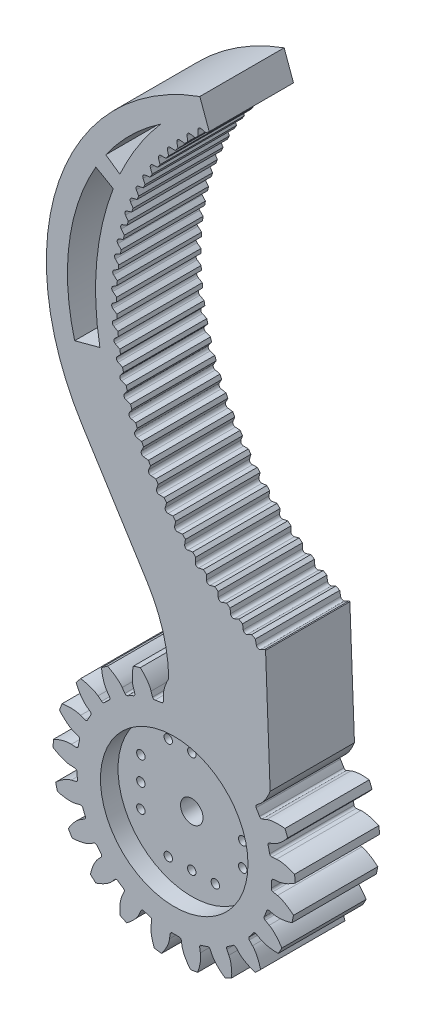
SolidWorks part; units mm, degrees
ref_plane "Спереди" through (0, 0, 0) normal (0, 0, 1) x (1, 0, 0)
ref_plane "Сверху" through (0, 0, 0) normal (0, 1, 0) x (1, 0, 0)
ref_plane "Справа" through (0, 0, 0) normal (1, 0, 0) x (0, 0, -1)
sketch "Эскиз1" plane through (0, 0, 0) normal (0, 0, 1) x (1, 0, 0)
  line L0 (15.6867, 1.4109) -> (0, 0) construction
  circle A0 centre (0, 0) radius 13.875
  circle A1 centre (0, 0) radius 14.8002
  circle A2 centre (0, 0) radius 15.75 construction
  circle A3 centre (0, 0) radius 17.25
  arc A4 (15.7483, 0.2347) -> (15.5374, 2.5792) centre (0, 0) ccw
  spline S0 degree 4 poles (14.8002, 0) (14.8458, 0.002) (14.9732, 0.0136) (15.2133, 0.0598) (15.5951, 0.1687) (16.0737, 0.3584) (16.6643, 0.6565) (17.3197, 1.0707) (17.995, 1.5895) (18.8399, 2.3661) (19.5994, 3.2279) (20.3031, 4.1917) (21.0383, 5.4087) (21.672, 6.6826) (22.2673, 8.2245) (22.7566, 9.9949) (23.0815, 11.8022) (23.2494, 13.6306) (23.2682, 15.4662) (23.1448, 17.2979) (22.8867, 19.1147) (22.5485, 20.6854) (22.2139, 21.9004) (21.9356, 22.776) (21.7516, 23.3151) (21.593, 23.7537) (21.4373, 24.1684) (21.2567, 24.6196) (21.1147, 24.9658) (20.9433, 25.3602) (20.7668, 25.7564) (20.5837, 26.1503) (20.2525, 26.8364) (19.9608, 27.3858) (19.6554, 27.9549) (19.4953, 28.2253) (19.392, 28.4076) knots 0 0 0 0 0 0.005604 0.015718 0.02996 0.048734 0.068727 0.096889 0.125051 0.153212 0.209535 0.237696 0.271429 0.327752 0.384075 0.440398 0.496721 0.553044 0.609367 0.66569 0.722013 0.778336 0.806497 0.820578 0.834659 0.84874 0.86282 0.876901 0.890982 0.900036 0.909091 0.931818 0.954545 0.977273 1 1 1 1 1 construction
  spline S1 degree 4 poles (14.8002, 0) (14.8458, 0.002) (14.9732, 0.0136) (15.2133, 0.0598) (15.5951, 0.1687) (16.0737, 0.3584) (16.6643, 0.6565) (17.3197, 1.0707) (17.995, 1.5895) (18.8399, 2.3661) (19.5994, 3.2279) (20.3031, 4.1917) (21.0383, 5.4087) (21.672, 6.6826) (22.2673, 8.2245) (22.7566, 9.9949) (23.0815, 11.8022) (23.2494, 13.6306) (23.2682, 15.4662) (23.1448, 17.2979) (22.8867, 19.1147) (22.5485, 20.6854) (22.2139, 21.9004) (21.9356, 22.776) (21.7516, 23.3151) (21.593, 23.7537) (21.4373, 24.1684) (21.2567, 24.6196) (21.1147, 24.9658) (20.9433, 25.3602) (20.8398, 25.5924) (20.7843, 25.7149) (20.7565, 25.7758) knots 0 0 0 0 0 0.005604 0.015718 0.02996 0.048734 0.068727 0.096889 0.125051 0.153212 0.209535 0.237696 0.271429 0.327752 0.384075 0.440398 0.496721 0.553044 0.609367 0.66569 0.722013 0.778336 0.806497 0.820578 0.834659 0.84874 0.86282 0.876901 0.890982 0.900036 0.909091 0.909091 0.909091 0.909091 0.909091
  dimension "D1" = 27.75
  dimension "D2" = 29.6003
  dimension "D3" = 31.5
  dimension "D4" = 34.5
  dimension "D5" = 2.3562
extrude "Бобышка-Вытянуть1" add sketch "Эскиз1" along normal mid plane 12 contours A0 region at (0, 0, 0)
sketch "Эскиз2" plane through (0, 0, 0) normal (0, 0, 1) x (1, 0, 0)
  line L0 (15.6867, 1.4109) -> (0, 0) construction
  line L1 (15.6867, 1.4109) -> (0, 0) construction
  line L2 (14.8002, 0) -> (13.8748, -0.0832)
  line L3 (14.5626, 2.6409) -> (13.6372, 2.5577)
  circle A0 centre (0, 0) radius 14.8002 construction
  circle A1 centre (0, 0) radius 14.8002
  circle A2 centre (0, 0) radius 13.875 construction
  circle A3 centre (0, 0) radius 13.875
extrude "Бобышка-Вытянуть2" add sketch "Эскиз2" along normal mid plane 12 contours L1 A1 L3 A3 | A1 L1 A3 L2 region at (14.3189, 0.6218, 0) region at (14.2001, 1.9432, 0)
sketch "Эскиз3" plane through (0, 0, 0) normal (0, 0, 1) x (1, 0, 0)
  line L0 (15.6867, 1.4109) -> (0, 0) construction
  line L1 (15.6867, 1.4109) -> (0, 0) construction
  circle A0 centre (0, 0) radius 17.25 construction
  circle A1 centre (0, 0) radius 14.8002 construction
  circle A2 centre (0, 0) radius 17.25
  circle A3 centre (0, 0) radius 14.8002
  spline S0 degree 4 poles (5.9786, 999.9569) (7.8641, 34.1268) (10.739, 0.6192) (13.3133, -0.4819) (15.5951, 0.1687) (16.0737, 0.3584) (16.6643, 0.6565) (17.3197, 1.0707) (17.995, 1.5895) (18.8399, 2.3661) (19.5994, 3.2279) (20.3031, 4.1917) (21.0383, 5.4087) (21.672, 6.6826) (22.2673, 8.2245) (22.7566, 9.9949) (23.0815, 11.8022) (23.2494, 13.6306) (23.2682, 15.4662) (23.1448, 17.2979) (22.8867, 19.1147) (22.5485, 20.6854) (22.2139, 21.9004) (21.9356, 22.776) (21.7516, 23.3151) (21.593, 23.7537) (21.4373, 24.1684) (21.2567, 24.6196) (21.1147, 24.9658) (19.98, 27.5761) (20.2039, 26.5951) (13.0579, 41.2248) (-396.3983, 934.5059) knots -0.242482 -0.242482 -0.242482 -0.242482 -0.242482 0.005604 0.015718 0.02996 0.048734 0.068727 0.096889 0.125051 0.153212 0.209535 0.237696 0.271429 0.327752 0.384075 0.440398 0.496721 0.553044 0.609367 0.66569 0.722013 0.778336 0.806497 0.820578 0.834659 0.84874 0.86282 0.876901 0.890982 0.900036 1.16908 1.16908 1.16908 1.16908 1.16908 only from (14.8002, 0) to (20.7565, 25.7758) construction
  spline S1 degree 4 poles (14.8002, 0) (14.8458, 0.002) (14.9732, 0.0136) (15.2133, 0.0598) (15.5951, 0.1687) (16.0737, 0.3584) (16.6643, 0.6565) (17.3197, 1.0707) (17.995, 1.5895) (18.8399, 2.3661) (19.5994, 3.2279) (20.3031, 4.1917) (21.0383, 5.4087) (21.672, 6.6826) (22.2673, 8.2245) (22.7566, 9.9949) (23.0815, 11.8022) (23.2494, 13.6306) (23.2682, 15.4662) (23.1448, 17.2979) (22.8867, 19.1147) (22.5485, 20.6854) (22.2139, 21.9004) (21.9356, 22.776) (21.7516, 23.3151) (21.593, 23.7537) (21.4373, 24.1684) (21.2567, 24.6196) (21.1147, 24.9658) (20.9433, 25.3602) (20.8398, 25.5924) (20.7843, 25.7149) (20.7565, 25.7758) knots 0 0 0 0 0 0.005604 0.015718 0.02996 0.048734 0.068727 0.096889 0.125051 0.153212 0.209535 0.237696 0.271429 0.327752 0.384075 0.440398 0.496721 0.553044 0.609367 0.66569 0.722013 0.778336 0.806497 0.820578 0.834659 0.84874 0.86282 0.876901 0.890982 0.900036 0.909091 0.909091 0.909091 0.909091 0.909091
  spline S2 degree 4 poles (14.5626, 2.6409) (14.6079, 2.6471) (14.7353, 2.6584) (14.9798, 2.6558) (15.3749, 2.6168) (15.8797, 2.5156) (16.514, 2.3276) (17.2328, 2.037) (17.9899, 1.647) (18.9597, 1.0336) (19.8608, 0.3212) (20.7252, -0.5016) (21.6658, -1.5679) (22.5166, -2.7082) (23.3776, -4.1192) (24.1749, -5.7738) (24.817, -7.4941) (25.3085, -9.2632) (25.6545, -11.066) (25.86, -12.8903) (25.9302, -14.7241) (25.8777, -16.3299) (25.7653, -17.585) (25.6477, -18.4963) (25.5629, -19.0596) (25.4851, -19.5194) (25.4058, -19.9552) (25.3087, -20.4315) (25.2307, -20.7975) (25.1324, -21.2161) (25.0721, -21.463) (25.0393, -21.5935) (25.0228, -21.6584) knots 0 0 0 0 0 0.005604 0.015718 0.02996 0.048734 0.068727 0.096889 0.125051 0.153212 0.209535 0.237696 0.271429 0.327752 0.384075 0.440398 0.496721 0.553044 0.609367 0.66569 0.722013 0.778336 0.806497 0.820578 0.834659 0.84874 0.86282 0.876901 0.890982 0.900036 0.909091 0.909091 0.909091 0.909091 0.909091 only from (13.85, 2.6188) to (23.9848, -20.4482)
extrude "Бобышка-Вытянуть3" add sketch "Эскиз3" along normal mid plane 12 contours A3 S1 A2 region at (15.7857, 1.4198, 0)
fillet "Скругление1" radius 0.3 2 edges at (13.6372, 2.5577, 0) (13.8748, -0.0832, 0)
pattern_circular "Круговой массив1" count 21 over 360 about axis through (0, 0, 6) along (0, 0, 1) of "Бобышка-Вытянуть3", "Скругление1", "Бобышка-Вытянуть2"
sketch "Эскиз4" plane through (0, 0, 6) normal (0, 0, 1) x (1, 0, 0)
  circle A0 centre (0, 0) radius 10.5
  dimension "D1" = 21
extrude "Вырез-Вытянуть1" cut sketch "Эскиз4" against normal blind 2.5
sketch "Эскиз5" plane through (0, 0, 3.5) normal (0, 0, 1) x (1, 0, 0)
  line L0 (-7.25, -7.25) -> (-7.25, 7.25) construction
  line L1 (-7.25, 7.25) -> (7.25, 7.25) construction
  line L2 (7.25, 7.25) -> (7.25, -7.25) construction
  line L3 (7.25, -7.25) -> (-7.25, -7.25) construction
  line L4 (-7.25, -7.25) -> (7.25, 7.25) construction
  line L5 (-3.35, 7.25) -> (-3.35, -7.25) construction
  line L6 (-7.25, 3.35) -> (7.25, 3.35) construction
  line L7 (3.35, 7.25) -> (3.35, -7.25) construction
  line L8 (7.25, -3.35) -> (-7.25, -3.35) construction
  line L9 (0, 3.35) -> (0, 0) construction
  line L10 (0, 0) -> (3.35, 0) construction
  line L11 (0, 0) -> (-3.35, 0) construction
  line L12 (0, 0) -> (0, -3.35) construction
  circle A0 centre (0, 7.25) radius 0.6
  circle A1 centre (-3.35, 7.25) radius 0.6
  circle A2 centre (3.35, 7.25) radius 0.6
  circle A3 centre (-7.25, 0) radius 0.6
  circle A4 centre (0, -7.25) radius 0.6
  circle A5 centre (7.25, 0) radius 0.6
  circle A6 centre (7.25, 3.35) radius 0.6
  circle A7 centre (7.25, -3.35) radius 0.6
  circle A8 centre (3.35, -7.25) radius 0.6
  circle A9 centre (-3.35, -7.25) radius 0.6
  circle A10 centre (-7.25, -3.35) radius 0.6
  circle A11 centre (-7.25, 3.35) radius 0.6
  point P2 (0, 0)
  dimension "D2" = 1.2
  dimension "D1" = 6.7
  dimension "D3" = 14.5
extrude "Вырез-Вытянуть2" cut sketch "Эскиз5" against normal blind 5
sketch "Эскиз6" plane through (0, 0, 3.5) normal (0, 0, 1) x (1, 0, 0)
  circle A0 centre (0, 0) radius 1.6
  dimension "D1" = 3.2
extrude "Вырез-Вытянуть3" cut sketch "Эскиз6" against normal through all
sketch "Эскиз7" plane through (0, 0, -6) normal (0, 0, -1) x (-1, 0, 0)
  circle A0 centre (0, 0) radius 5.125
  dimension "D1" = 10.25
extrude "Вырез-Вытянуть4" cut sketch "Эскиз7" against normal blind 4.5
sketch "Эскиз8" plane through (0, 0, 0) normal (0, 0, 1) x (1, 0, 0)
  line L0 (15, 0) -> (15, 60) construction
  line L1 (15, 60) -> (15, 83.2) construction
  line L2 (15, 60) -> (3.6449, 91.1978) construction
  line L3 (3.6449, 91.1978) -> (4.9781, 87.5348)
  line L4 (0, 0) -> (13.3248, 10.955) construction
  line L5 (0, 0) -> (-0.257, 17.2481) construction
  line L6 (9.2695, 7.6208) -> (13, 10.6879) construction
  line L7 (13, 10.6879) -> (13, 27.6022) construction
  line L8 (-0.1788, 11.9987) -> (-0.3278, 21.9976) construction
  line L9 (-0.3278, 21.9976) -> (-13.109, 42.3329)
  line L11 (13.6523, 10.5441) -> (9.2695, 7.6208)
  line L12 (-0.3278, 21.9976) -> (-0.7822, 17.2323)
  line L13 (-0.7822, 17.2323) -> (-0.1788, 11.9987)
  line L18 (10, 11.7141) -> (10, 11.7141) construction
  line L20 (-1.92, 85.0151) -> (-1.92, 85.0151)
  line L21 (-9.7384, 77.322) -> (-7.7391, 75.9221)
  line L22 (15, 60) -> (-8.2, 60) construction
  line L23 (-8.6805, 73.672) -> (-11.154, 75.1)
  line L24 (-14.171, 52.1837) -> (-10.5825, 53.1452)
  line L26 (13, 27.6022) -> (13.6523, 10.5441)
  line L28 (10, 11.7141) -> (10, 25.6952) construction
  line L29 (10, 11.7141) -> (9.6521, 11.4821) construction
  line L30 (2.2342, 17.262) -> (2.5196, 14.7869) construction
  line L31 (2.7556, 22.7294) -> (2.2342, 17.262) construction
  line L32 (2.7556, 22.7294) -> (-10.569, 43.9294) construction
  line L33 (13, 10.6879) -> (13.6523, 10.5441) construction
  circle A0 centre (0, 0) radius 15 construction
  circle A1 centre (30, 0) radius 15 construction
  circle A2 centre (15, 60) radius 33.2 construction
  circle A3 centre (15, 60) radius 23.2 construction
  arc A4 (13, 27.6022) -> (4.9781, 87.5348) centre (27.1552, 60) cw
  arc A5 (13.6523, 10.5441) -> (12.985, 11.3557) centre (0, 0) ccw construction
  arc A6 (0.2684, 17.2479) -> (-0.7822, 17.2323) centre (0, 0) ccw construction
  arc A7 (-0.1788, 11.9987) -> (9.2695, 7.6208) centre (0, 0) cw
  arc A8 (15, 26.8) -> (15, 93.2) centre (27.1552, 60) cw construction
  arc A9 (3.6449, 91.1978) -> (-13.109, 42.3329) centre (15, 60) ccw
  arc A10 (-1.92, 85.0151) -> (-9.7384, 77.322) centre (15, 60) ccw
  arc A13 (-7.7391, 75.9221) -> (-1.92, 85.0151) centre (27.1552, 60) cw
  arc A14 (10, 25.6952) -> (-1.92, 85.0151) centre (27.1552, 60) cw construction
  arc A15 (-11.154, 75.1) -> (-14.171, 52.1837) centre (15, 60) ccw
  arc A16 (-1.92, 85.0151) -> (-10.569, 43.9294) centre (15, 60) ccw construction
  arc A18 (-10.5825, 53.1452) -> (-8.6805, 73.672) centre (27.1552, 60) cw
  arc A19 (2.5196, 14.7869) -> (9.6521, 11.4821) centre (0, 0) cw construction
  dimension "D1" = 30
  dimension "D2" = 66.4
  dimension "D4" = 46.4
  dimension "D6" = 35.3552
  dimension "D7" = 12
  dimension "D3" = 60
  dimension "D5" = 20
  dimension "D8" = 2
  dimension "D9" = 10
  dimension "D11" = 35
  dimension "D12" = 30
  dimension "D13" = 15
  dimension "D10" = 3
extrude "Бобышка-Вытянуть4" add sketch "Эскиз8" along normal mid plane 12
fillet "Скругление2" radius 20 1 edges at (-0.3278, 21.9976, 0)
sketch "Эскиз9" plane through (0, 0, 0) normal (0, 0, 1) x (1, 0, 0)
  line L0 (27.1552, 60) -> (11.7908, 27.051) construction
  line L1 (11.7908, 27.051) -> (14.1707, 28.3687)
  line L2 (14.1707, 28.3687) -> (11.2705, 29.7211)
  line L3 (11.2705, 29.7211) -> (11.7908, 27.051)
  line L4 (27.1552, 60) -> (27.1552, 24.6448) construction
  circle A0 centre (27.1552, 60) radius 35.3552 construction
  arc A1 (4.9781, 87.5348) -> (13, 27.6022) centre (27.1552, 60) ccw construction
  circle A2 centre (27.1552, 60) radius 36.3552 construction
  point P7 (12.7206, 29.0449)
  dimension "D2" = 3.2
  dimension "D3" = 2.2
  dimension "D4" = 25
  dimension "D1" = 1
extrude "Вырез-Вытянуть5" cut sketch "Эскиз9" against normal mid plane 12
fillet "Скругление3" radius 0.4 1 edges at (11.7908, 27.051, 0)
pattern_circular "Круговой массив2" count 35 over 114 about axis through (27.1552, 60, 6) along (0, 0, -1) of "Вырез-Вытянуть5", "Скругление3"
ref_plane "Плоскость1" [suppressed] through (20, 0, 0) normal (1, 0, 0) x (0, 0, -1)
mirror "Зеркальное отражение1" [suppressed] about plane through (20, 0, 0) normal (1, 0, 0) of bodies 113
delete or keep bodies "Тело-Удалить/Сохранить 1" [suppressed] bodies 113
equation "\"m\"= 1.5"
equation "\"z\"= 21"
equation "\"b\"= 12"
equation "\"a\"= 20 * pi / 180"
equation "\"D\"= \"m\" * \"z\""
equation "\"Db\"= \"D\" * cos ( \"a\" )"
equation "\"Da\"= \"D\" + \"m\" * 2"
equation "\"Df\"= \"D\" - \"m\" * 2.5"
equation "\"S\"= \"m\" * pi / 2"
equation "\"D1@Эскиз1\"=\"Df\""
equation "\"D2@Эскиз1\"=\"Db\""
equation "\"D3@Эскиз1\"=\"D\""
equation "\"D4@Эскиз1\"=\"Da\""
equation "\"D5@Эскиз1\"=\"S\""
equation "\"D1@Бобышка-Вытянуть1\"=\"b\""
equation "\"D1@Бобышка-Вытянуть2\"=\"b\""
equation "\"D1@Бобышка-Вытянуть3\"=\"b\""
equation "\"D1@Скругление1\"=\"m\"*0.2"
equation "\"D1@Круговой массив1\"=\"z\""
equation "\"D1@Бобышка-Вытянуть4\"=\"b\""
equation "\"D1@Вырез-Вытянуть5\"=\"b\""
